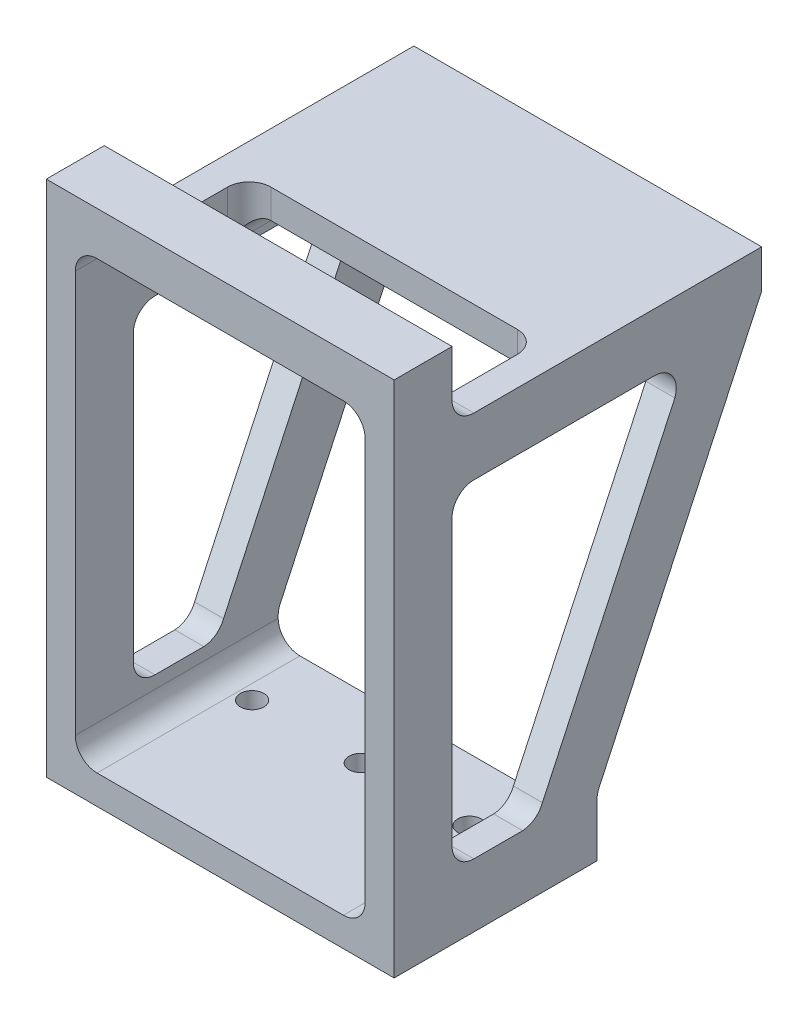
SolidWorks part; units mm, degrees
ref_plane "Front Plane" through (0, 0, 0) normal (0, 0, 1) x (1, 0, 0)
ref_plane "Top Plane" through (0, 0, 0) normal (0, 1, 0) x (1, 0, 0)
ref_plane "Right Plane" through (0, 0, 0) normal (1, 0, 0) x (0, 0, -1)
sketch "Sketch1" plane through (0, 0, 0) normal (0, 1, 0) x (1, 0, 0)
  line L0 (0, 148.354) -> (0, -12.7) construction
  line L2 (-76.2, 148.354) -> (-76.2, -12.7)
  line L3 (-76.2, -12.7) -> (76.2, -12.7)
  line L4 (76.2, 148.354) -> (76.2, -12.7)
  line L5 (76.2, 148.354) -> (-76.2, 148.354)
  dimension "D1" = 12.7
  dimension "D2" = 152.4
  dimension "D3" = 161.054
extrude "Boss-Extrude1" add sketch "Sketch1" along normal blind 179.05 and the other way blind 139.192
ref_plane "Plane1" through (0, -47.895, 0) normal (0, 1, 0) x (1, 0, 0)
other "SurfaceCut1"
sketch "Sketch3" plane through (0, 0, 0) normal (1, 0, 0) x (0, 0, -1)
  line L0 (-12.7, -47.895) -> (148.354, -47.895) construction
  line L1 (0, -38.37) -> (75, -38.37)
  line L2 (0, -38.37) -> (0, -47.895)
  line L3 (0, -47.895) -> (75, -47.895)
  line L4 (75, -38.37) -> (75, -47.895)
  dimension "D1" = 9.525
  dimension "D2" = 75
extrude "Boss-Extrude2" add sketch "Sketch3" along normal up to surface and the other way up to surface up to face at (76.2, 65.5775, -67.827) other way up to face at (-76.2, 65.5775, -67.827)
sketch "Sketch5" plane through (0, 0, 0) normal (0, 1, 0) x (1, 0, 0)
  line L0 (0, 48.895) -> (0, 23.495) construction
  line L9 (-47.625, 48.895) -> (-47.625, 23.495)
  line L11 (47.625, 23.495) -> (47.625, 48.895)
  line L17 (-47.625, 23.495) -> (47.625, 23.495) construction
  line L19 (47.625, 48.895) -> (-47.625, 48.895) construction
  dimension "D1" = 95.25
  dimension "D2" = 25.4
  dimension "D3" = 23.495
hole_wizard "3/8 Clearance Hole1" positions "Sketch6" profile "Sketch7" hole size "3/8" standard "ANSI Inch" end condition through all
sketch "Sketch6" plane through (0, -47.895, 0) normal (0, 1, 0) x (1, 0, 0)
  line L0 (47.625, 48.895) -> (-47.625, 48.895) construction
  point P0 (47.625, 48.895)
  point P4 (-47.625, 48.895)
  point P6 (0, 48.895)
sketch "Sketch7" plane through (47.625, -47.895, -48.895) normal (1, 0, 0) x (0, 0, -1)
  line L0 (0, 0) -> (0, 226.945)
  line L1 (0, 226.945) -> (5.1587, 226.945)
  line L2 (5.1587, 226.945) -> (5.1587, 0)
  line L5 (5.1587, 0) -> (0, 0)
  line L11 (0, -6.35) -> (0, 107.95) construction
  dimension "Thru Hole Dia." = 10.3175
  dimension "Thru Hole Depth" = 226.945
sketch "Sketch4" [suppressed] plane through (76.2, 0, 0) normal (1, 0, 0) x (0, 0, -1)
  line L0 (9.525, 179.05) -> (75, 45.7)
rib "Rib1" [suppressed] sketch "Sketch4" sketch "Sketch4" thickness 9.525 extrusion direction parallel to sketch draft on no parameters "D1"=9.525
mirror "Mirror1" [suppressed] about plane through (0, 0, 0) normal (1, 0, 0)
sketch "Sketch8" plane through (0, 0, 0) normal (1, 0, 0) x (0, 0, -1)
  line L0 (-295, 149.025) -> (-405, 149.025) construction
  line L1 (266.7, 301.425) -> (12.7, 301.425)
  line L2 (266.7, 301.425) -> (266.7, 149.025)
  line L3 (266.7, 149.025) -> (12.7, 149.025)
  line L4 (12.7, 301.425) -> (12.7, 149.025)
  dimension "D1" = 12.7
  dimension "D2" = 152.4
  dimension "D3" = 254
extrude "Cut-Extrude1" cut sketch "Sketch8" against normal through all both and the other way through all
fillet "Fillet1" radius 9.525 1 edges at (0, 149.025, -12.7)
sketch "Sketch10" plane through (0, 149.025, 0) normal (0, 1, 0) x (1, 0, 0)
  line L20 (0, 63.5) -> (0, 12.7) construction
  line L21 (63.5, 63.5) -> (-63.5, 63.5)
  line L22 (63.5, 63.5) -> (63.5, 12.7)
  line L23 (63.5, 12.7) -> (-63.5, 12.7)
  line L24 (-63.5, 63.5) -> (-63.5, 12.7)
  line L25 (76.2, 22.225) -> (76.2, 148.354) construction
  line L26 (76.2, 12.7) -> (-76.2, 12.7) construction
  dimension "D1" = 12.7
  dimension "D2" = 50.8
extrude "Cut-Extrude2" cut sketch "Sketch10" against normal offset from surface 12.7 and the other way blind 101.6 up to face at (47.625, -47.895, -54.0537)
fillet "Fillet2" radius 9.525 4 edges at (-63.5, 56.915, -63.5) (-63.5, 61.6775, -12.7) (63.5, 61.6775, -12.7) (63.5, 56.915, -63.5)
sketch "Sketch11" plane through (0, 0, 0) normal (1, 0, 0) x (0, 0, -1)
  line L0 (279.4, 413.2688) -> (76.2, -22.495)
  line L1 (279.4, 413.2688) -> (279.4, -78.833)
  line L2 (279.4, -78.833) -> (76.2, -78.833)
  line L3 (76.2, -22.495) -> (76.2, -78.833)
  line L4 (-12.7, 179.05) -> (-12.7, -47.895) construction
  line L5 (148.354, -47.895) -> (-12.7, -47.895) construction
  dimension "D1" = 65
  dimension "D2" = 88.9
  dimension "D3" = 25.4
  dimension "D4" = 203.2
extrude "Cut-Extrude3" cut sketch "Sketch11" against normal through all both and the other way through all
fillet "Fillet3" radius 9.525 1 edges at (0, -22.495, -76.2)
sketch "Sketch14" plane through (0, 0, -148.354) normal (0, 0, -1) x (-1, 0, 0)
  line L0 (0, 136.325) -> (0, -35.195) construction
  line L1 (-63.5, 136.325) -> (63.5, 136.325)
  line L2 (-63.5, 136.325) -> (-63.5, -35.195)
  line L3 (-63.5, -35.195) -> (63.5, -35.195)
  line L4 (63.5, 136.325) -> (63.5, -35.195)
  line L6 (76.2, 149.025) -> (-76.2, 149.025) construction
  line L9 (76.2, -47.895) -> (-76.2, -47.895) construction
  line L10 (-76.2, 132.2398) -> (-76.2, 149.025) construction
  dimension "D1" = 12.7
  dimension "D2" = 12.7
  dimension "D3" = 12.7
extrude "Cut-Extrude4" cut sketch "Sketch14" against normal up to surface (135.654 mm away) up to face at (0, 115.2388, -12.7)
sketch "Sketch15" plane through (0, 0, 0) normal (0, 0, 1) x (1, 0, 0)
  line L0 (0, 160) -> (0, -35.195) construction
  line L1 (63.5, 160) -> (-63.5, 160)
  line L2 (63.5, 160) -> (63.5, -35.195)
  line L3 (63.5, -35.195) -> (-63.5, -35.195)
  line L4 (-63.5, 160) -> (-63.5, -35.195)
  line L5 (-76.2, 179.05) -> (76.2, 179.05) construction
  line L7 (-63.5, -35.195) -> (-63.5, 136.325) construction
  line L8 (63.5, -35.195) -> (-63.5, -35.195) construction
  dimension "D1" = 19.05
extrude "Cut-Extrude5" cut sketch "Sketch15" along normal through all and the other way blind 25.4
fillet "Fillet5" radius 9.525 6 edges at (63.5, 160, 0) (-63.5, 160, 0) (-63.5, 136.325, -101.1645) (63.5, 136.325, -101.1645) (63.5, -35.195, -31.75) (-63.5, -35.195, -31.75)
sketch "Sketch16" plane through (0, 0, 0) normal (1, 0, 0) x (0, 0, -1)
  line L6 (12.7, -22.495) -> (50.8639, -22.495)
  line L7 (22.225, -20.1525) -> (43.6105, -20.1525)
  line L8 (54.0722, -9.8467) -> (116.3111, 123.625)
  line L9 (52.2795, -13.8365) -> (110.2895, 110.6975)
  line L18 (12.7, 124.949) -> (12.7, -22.495)
  line L19 (116.3111, 123.625) -> (22.225, 123.625)
  line L22 (12.7, 114.1) -> (12.7, -10.6275)
  line L23 (101.3929, 123.625) -> (22.225, 123.625)
  arc A0 (43.6105, -20.1525) -> (52.2795, -13.8365) centre (43.0272, -10.2447) ccw
  arc A3 (22.225, -20.1525) -> (12.7, -10.6275) centre (22.225, -10.6275) cw
  arc A4 (54.0722, -9.8467) -> (50.8639, -22.495) centre (85.725, -24.6066) ccw
  arc A5 (12.7, 124.949) -> (22.225, 123.625) centre (22.225, 158.55) ccw
  arc A8 (22.225, 123.625) -> (12.7, 114.1) centre (22.225, 114.1) ccw
  arc A9 (110.2895, 110.6975) -> (101.3929, 123.625) centre (101.3929, 114.1) ccw
  dimension "D1" = 25.4
extrude "Cut-Extrude6" cut sketch "Sketch16" against normal through all both and the other way through all
